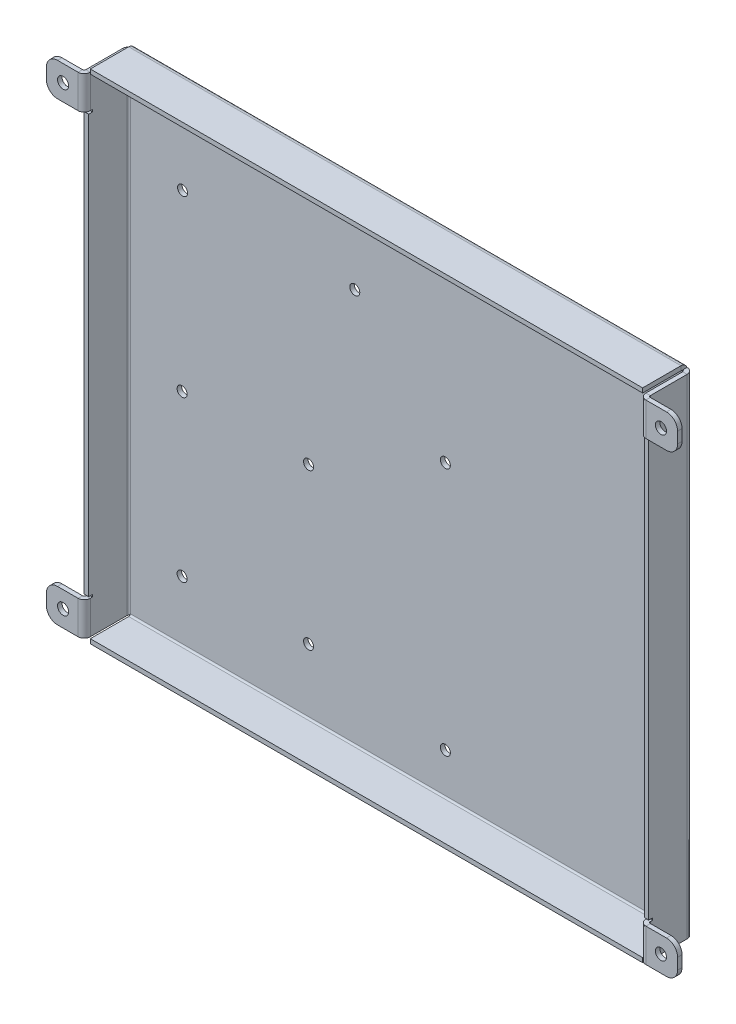
SolidWorks part; units mm, degrees
note: The reader was unsure of these and kept them because the rebuilt part matched: flange length of "Edge-Flange1", "Edge-Flange2", "Edge-Flange3", "Edge-Flange4", "Edge-Flange5", "Edge-Flange7", "Edge-Flange8".
ref_plane "Front Plane" through (0, 0, 0) normal (0, 0, 1) x (1, 0, 0)
ref_plane "Top Plane" through (0, 0, 0) normal (0, 1, 0) x (1, 0, 0)
ref_plane "Right Plane" through (0, 0, 0) normal (1, 0, 0) x (0, 0, -1)
sketch "Sketch1" plane through (0, 0, 0) normal (0, 0, 1) x (1, 0, 0)
  line L1 (-125, 110) -> (125, 110)
  line L2 (-125, 110) -> (-125, -110)
  line L3 (-125, -110) -> (125, -110)
  line L4 (125, 110) -> (125, -110)
  line L5 (0, -110) -> (0, 110) construction
  line L6 (-125, 0) -> (125, 0) construction
  point P0 (0, 0)
  dimension "D1" = 250
  dimension "D2" = 220
base flange "Base-Flange1" sketch "Sketch1" thickness 2 reverse thickness direction no parameters "D1"=0.7366
edge flange "Edge-Flange1" sketch "Sketch10" flange profiles "Sketch10", "Sketch11" flange angle 90 flange length 20 flange position material outside bend radius 0.7366 thickness 2 relief rectangular parameters "D6"=10, "D8"=1
sketch "Sketch10" plane through (125, 0, 0) normal (-1, 0, 0) x (0, -1, 0)
  line L2 (-110, 0) -> (-110, 18)
  line L3 (-110, 18) -> (110, 18)
  line L4 (110, 18) -> (110, 0)
  line L5 (110, 0) -> (-110, 0) construction
  line L6 (110, 0) -> (-110, 0)
sketch "Sketch11" plane through (-125, 0, 0) normal (1, 0, 0) x (0, 1, 0)
  line L0 (110, 0) -> (-110, 0) construction
  line L1 (110, 0) -> (-110, 0)
  line L2 (110, 0) -> (110, 18)
  line L3 (110, 18) -> (-110, 18)
  line L4 (-110, 18) -> (-110, 0)
bend "EdgeBend1" bend radius 0.7366 bend angle 90 parameters "D5"=1
bend "EdgeBend2" bend radius 0.7366 bend angle 90 parameters "D5"=2
edge flange "Edge-Flange2" sketch "Sketch14" flange angle 90 flange length 20 flange position material outside bend radius 0.7366 thickness 2 relief none parameters "D6"=10
sketch "Sketch14" plane through (0, 110, 0) normal (0, -1, 0) x (1, 0, 0)
  line L2 (-124.2634, 0) -> (-124.2634, 18)
  line L3 (-124.2634, 18) -> (124.2634, 18)
  line L4 (124.2634, 18) -> (124.2634, 0)
  line L5 (124.2634, 0) -> (-124.2634, 0) construction
  line L6 (124.2634, 0) -> (-124.2634, 0)
bend "EdgeBend3" bend radius 0.7366 bend angle 90 parameters "D5"=3
edge flange "Edge-Flange3" sketch "Sketch17" flange angle 90 flange length 20 flange position material outside bend radius 0.7366 thickness 2 relief none parameters "D6"=10
sketch "Sketch17" plane through (0, -110, 0) normal (0, -1, 0) x (1, 0, 0)
  line L0 (-124.2634, 0) -> (124.2634, 0) construction
  line L1 (-124.2634, 0) -> (124.2634, 0)
  line L2 (-124.2634, 0) -> (-124.2634, 18)
  line L3 (-124.2634, 18) -> (124.2634, 18)
  line L4 (124.2634, 18) -> (124.2634, 0)
bend "EdgeBend4" bend radius 0.7366 bend angle 90 parameters "D5"=4
edge flange "Edge-Flange4" sketch "Sketch20" flange angle 90 flange length 17 flange position material outside bend radius 0.7366 thickness 2 relief rectangular parameters "D6"=10
sketch "Sketch20" plane through (127, 0, 18) normal (0, 0, 1) x (0, -1, 0)
  line L0 (110, 0) -> (-110, 0) construction
  line L1 (110, 0) -> (95, 0)
  line L2 (95, 0) -> (95, 10)
  line L3 (100, 15) -> (105, 15)
  line L4 (110, 10) -> (110, 0)
  line L5 (110, 15) -> (95, 0) construction
  circle A0 centre (102.5, 7.5) radius 2.5
  arc A1 (105, 15) -> (110, 10) centre (105, 10) cw
  arc A2 (95, 10) -> (100, 15) centre (100, 10) cw
  point P12 (95, 15)
  dimension "D2" = 5
  dimension "D3" = 5
  dimension "D1" = 15
bend "EdgeBend5" bend radius 0.7366 bend angle 90 parameters "D5"=5
edge flange "Edge-Flange5" sketch "Sketch23" flange angle 90 flange length 17 flange position material outside bend radius 0.7366 thickness 2 relief rectangular parameters "D6"=10
sketch "Sketch23" plane through (127, 0, 18) normal (0, 0, 1) x (0, -1, 0)
  line L2 (-110, 0) -> (-110, 10)
  line L3 (-105, 15) -> (-100, 15)
  line L4 (-95, 10) -> (-95, 0)
  line L7 (94, 0) -> (-110, 0) construction
  line L8 (-95, 0) -> (-110, 0)
  line L9 (-110, 15) -> (-95, 0) construction
  circle A0 centre (-102.5, 7.5) radius 2.5
  arc A1 (-100, 15) -> (-95, 10) centre (-100, 10) cw
  arc A2 (-110, 10) -> (-105, 15) centre (-105, 10) cw
  point P9 (-95, 15)
  dimension "D2" = 5
  dimension "D3" = 5
  dimension "D1" = 15
bend "EdgeBend6" bend radius 0.7366 bend angle 90 parameters "D5"=6
edge flange "Edge-Flange7" sketch "Sketch30" flange angle 90 flange length 17 flange position material outside bend radius 0.7366 thickness 2 relief rectangular parameters "D6"=10
sketch "Sketch30" plane through (-127, 0, 18) normal (0, 0, 1) x (0, 1, 0)
  line L0 (110, 0) -> (-110, 0) construction
  line L1 (-95, 0) -> (-110, 0)
  line L2 (-110, 0) -> (-110, 10)
  line L3 (-105, 15) -> (-100, 15)
  line L4 (-95, 10) -> (-95, 0)
  line L5 (-110, 0) -> (-95, 15) construction
  circle A0 centre (-102.5, 7.5) radius 2.5
  arc A1 (-100, 15) -> (-95, 10) centre (-100, 10) cw
  arc A2 (-110, 10) -> (-105, 15) centre (-105, 10) cw
  point P12 (-110, 15)
  dimension "D2" = 5
  dimension "D3" = 5
  dimension "D1" = 15
bend "EdgeBend8" bend radius 0.7366 bend angle 90 parameters "D5"=7
edge flange "Edge-Flange8" sketch "Sketch33" flange angle 90 flange length 17 flange position material outside bend radius 0.7366 thickness 2 relief rectangular parameters "D6"=10
sketch "Sketch33" plane through (-127, 0, 18) normal (0, 0, 1) x (0, 1, 0)
  line L2 (95, 0) -> (95, 10)
  line L3 (100, 15) -> (105, 15)
  line L4 (110, 10) -> (110, 0)
  line L7 (110, 0) -> (-94, 0) construction
  line L8 (110, 0) -> (95, 0)
  line L9 (110, 15) -> (95, 0) construction
  circle A0 centre (102.5, 7.5) radius 2.5
  arc A1 (105, 15) -> (110, 10) centre (105, 10) cw
  arc A2 (95, 10) -> (100, 15) centre (100, 10) cw
  point P12 (95, 15)
  dimension "D2" = 5
  dimension "D3" = 5
  dimension "D1" = 15
bend "EdgeBend9" bend radius 0.7366 bend angle 90 parameters "D5"=8
sketch "Sketch34" plane through (0, 0, 0) normal (0, 0, 1) x (1, 0, 0)
  circle A0 centre (-44.05, -11) radius 2.25
  circle A1 centre (-44.05, -80.9579) radius 2.25
  circle A2 centre (-100.95, -83) radius 2.25
  circle A3 centre (-100.95, -11) radius 2.25
  dimension "D1" = 4.5
  dimension "D2" = 4.5
  dimension "D3" = 4.5
  dimension "D4" = 4.5
extrude "Cut-Extrude1" cut sketch "Sketch34" against normal blind 10
sketch "Sketch35" plane through (0, 0, -2) normal (0, 0, -1) x (-1, 0, 0)
  circle A0 centre (100.75, 67.5) radius 2.25
  circle A1 centre (23.25, 67.5) radius 2.25
  circle A2 centre (-110, 90.5) radius 2.25
  circle A3 centre (-17.5, 20.5) radius 2.25
  circle A4 centre (-110, -21.5) radius 2.25
  circle A5 centre (-17.5, -91.5) radius 2.25
  dimension "D1" = 4.5
  dimension "D2" = 4.5
  dimension "D3" = 4.5
  dimension "D4" = 4.5
  dimension "D5" = 4.5
  dimension "D6" = 4.5
extrude "Cut-Extrude2" cut sketch "Sketch35" against normal blind 10
sketch "Bend-Lines1" [suppressed] plane through (0, 0, 0) normal (0, 1, 0) x (1, 0, 0)
sketch "Bounding-Box1" [suppressed] plane through (0, 0, 0) normal (0, 1, 0) x (1, 0, 0)
sheet metal parameters "Sheet-Metal1" thickness 2 parameters "D1"=0.7366
flat pattern "Flat-Pattern1" [suppressed]
sketch "Bend-Lines2" plane through (0, 0, 0) normal (0, 1, 0) x (1, 0, 0)
sketch3d "Bounding-Box2" [suppressed]
  line L0 (150, -87.5, 0) -> (-150, -87.5, 0) construction
  line L1 (150, 87.5, 0) -> (-150, 87.5, 0) construction
  line L2 (150, -87.5, 0) -> (150, 87.5, 0) construction
  line L3 (-150, -87.5, 0) -> (-150, 87.5, 0) construction
sheet metal parameters "Sheet-Metal2" thickness 2 parameters "D1"=0.7366
flat pattern "Flat-Pattern1"
sketch "Bend-Lines2" plane through (0, 0, 0) normal (0, 0, 1) x (1, 0, 0)
  line L0 (-150.3132, 87.5) -> (-150.3132, -87.5) construction
  line L1 (150.3132, -87.5) -> (150.3132, 87.5) construction
  line L2 (-150.3132, 87.5) -> (-150.3132, -87.5) construction
  line L3 (150.3132, -87.5) -> (150.3132, 87.5) construction
sketch3d "Bounding-Box2" [suppressed]
  line L0 (-168.6263, -87.5, 0) -> (168.6263, -87.5, 0) construction
  line L1 (-168.6263, 87.5, 0) -> (168.6263, 87.5, 0) construction
  line L2 (-168.6263, -87.5, 0) -> (-168.6263, 87.5, 0) construction
  line L3 (168.6263, -87.5, 0) -> (168.6263, 87.5, 0) construction
bend of the flat pattern "Flatten-<EdgeBend1>1"
bend of the flat pattern "Flatten-<EdgeBend2>1"
sheet metal parameters "Sheet-Metal3" thickness 2 parameters "D1"=0.7366
flat pattern "Flat-Pattern1"
sketch "Bend-Lines2" plane through (0, 0, 0) normal (0, 0, 1) x (1, 0, 0)
  line L0 (-150.3132, 87.5) -> (-150.3132, -87.5) construction
  line L1 (150.3132, -87.5) -> (150.3132, 87.5) construction
  line L2 (-150.3132, 87.5) -> (-150.3132, -87.5) construction
  line L3 (150.3132, -87.5) -> (150.3132, 87.5) construction
  line L4 (149.2634, 87.8132) -> (-149.2634, 87.8132) construction
  line L5 (149.2634, 87.8132) -> (-149.2634, 87.8132) construction
sketch3d "Bounding-Box2" [suppressed]
  line L0 (-168.6263, -87.5, 0) -> (168.6263, -87.5, 0) construction
  line L1 (-168.6263, 106.1263, 0) -> (168.6263, 106.1263, 0) construction
  line L2 (-168.6263, -87.5, 0) -> (-168.6263, 106.1263, 0) construction
  line L3 (168.6263, -87.5, 0) -> (168.6263, 106.1263, 0) construction
bend of the flat pattern "Flatten-<EdgeBend1>1"
bend of the flat pattern "Flatten-<EdgeBend2>1"
bend of the flat pattern "Flatten-<EdgeBend3>1"
sheet metal parameters "Sheet-Metal4" thickness 2 parameters "D1"=0.7366
flat pattern "Flat-Pattern1"
sketch "Bend-Lines2" plane through (0, 0, 0) normal (0, 0, 1) x (1, 0, 0)
  line L0 (-150.3132, 110) -> (-150.3132, -110) construction
  line L1 (150.3132, -110) -> (150.3132, 110) construction
  line L2 (-150.3132, 110) -> (-150.3132, -110) construction
  line L3 (150.3132, -110) -> (150.3132, 110) construction
  line L4 (149.2634, 110.3132) -> (-149.2634, 110.3132) construction
  line L5 (149.2634, 110.3132) -> (-149.2634, 110.3132) construction
  line L6 (-149.2634, -110.3132) -> (149.2634, -110.3132) construction
  line L7 (-149.2634, -110.3132) -> (149.2634, -110.3132) construction
sketch3d "Bounding-Box2" [suppressed]
  line L0 (-168.6263, -128.6263, 0) -> (168.6263, -128.6263, 0) construction
  line L1 (-168.6263, 128.6263, 0) -> (168.6263, 128.6263, 0) construction
  line L2 (-168.6263, -128.6263, 0) -> (-168.6263, 128.6263, 0) construction
  line L3 (168.6263, -128.6263, 0) -> (168.6263, 128.6263, 0) construction
bend of the flat pattern "Flatten-<EdgeBend1>1"
bend of the flat pattern "Flatten-<EdgeBend2>1"
bend of the flat pattern "Flatten-<EdgeBend3>1"
bend of the flat pattern "Flatten-<EdgeBend4>1"
sheet metal parameters "Sheet-Metal5" thickness 2 parameters "D1"=0.7366
flat pattern "Flat-Pattern1"
sketch "Bend-Lines2" plane through (0, 0, 0) normal (0, 0, 1) x (1, 0, 0)
  line L0 (-150.3132, 110) -> (-150.3132, -110) construction
  line L1 (150.3132, -110) -> (150.3132, 110) construction
  line L2 (-150.3132, 110) -> (-150.3132, -110) construction
  line L3 (150.3132, -110) -> (150.3132, 110) construction
  line L4 (149.2634, 110.3132) -> (-149.2634, 110.3132) construction
  line L5 (149.2634, 110.3132) -> (-149.2634, 110.3132) construction
  line L6 (-149.2634, -110.3132) -> (149.2634, -110.3132) construction
  line L7 (-149.2634, -110.3132) -> (149.2634, -110.3132) construction
  line L8 (168.9395, -110) -> (168.9395, -93.0621) construction
  line L9 (168.9395, -110) -> (168.9395, -93.0621) construction
sketch3d "Bounding-Box2" [suppressed]
  line L0 (-168.6263, -128.6263, 0) -> (184.2527, -128.6263, 0) construction
  line L1 (-168.6263, 128.6263, 0) -> (184.2527, 128.6263, 0) construction
  line L2 (-168.6263, -128.6263, 0) -> (-168.6263, 128.6263, 0) construction
  line L3 (184.2527, -128.6263, 0) -> (184.2527, 128.6263, 0) construction
bend of the flat pattern "Flatten-<EdgeBend1>1"
bend of the flat pattern "Flatten-<EdgeBend2>1"
bend of the flat pattern "Flatten-<EdgeBend3>1"
bend of the flat pattern "Flatten-<EdgeBend4>1"
bend of the flat pattern "Flatten-<EdgeBend5>1"
sheet metal parameters "Sheet-Metal6" thickness 2 parameters "D1"=0.7366
flat pattern "Flat-Pattern1"
sketch "Bend-Lines2" plane through (0, 0, 0) normal (0, 0, 1) x (1, 0, 0)
  line L0 (-150.3132, 110) -> (-150.3132, -110) construction
  line L1 (150.3132, -110) -> (150.3132, 110) construction
  line L2 (-150.3132, 110) -> (-150.3132, -110) construction
  line L3 (150.3132, -110) -> (150.3132, 110) construction
  line L4 (149.2634, 110.3132) -> (-149.2634, 110.3132) construction
  line L5 (149.2634, 110.3132) -> (-149.2634, 110.3132) construction
  line L6 (-149.2634, -110.3132) -> (149.2634, -110.3132) construction
  line L7 (-149.2634, -110.3132) -> (149.2634, -110.3132) construction
  line L8 (168.9395, -110) -> (168.9395, -95) construction
  line L9 (168.9395, -110) -> (168.9395, -95) construction
  line L10 (168.9395, 95) -> (168.9395, 110) construction
  line L11 (168.9395, 95) -> (168.9395, 110) construction
sketch3d "Bounding-Box2" [suppressed]
  line L0 (-168.6263, 128.6264, 0) -> (184.2527, 128.6263, 0) construction
  line L1 (-168.6263, -128.6263, 0) -> (184.2526, -128.6263, 0) construction
  line L2 (-168.6263, 128.6264, 0) -> (-168.6263, -128.6263, 0) construction
  line L3 (184.2527, 128.6263, 0) -> (184.2526, -128.6263, 0) construction
bend of the flat pattern "Flatten-<EdgeBend1>1"
bend of the flat pattern "Flatten-<EdgeBend2>1"
bend of the flat pattern "Flatten-<EdgeBend3>1"
bend of the flat pattern "Flatten-<EdgeBend4>1"
bend of the flat pattern "Flatten-<EdgeBend5>1"
bend of the flat pattern "Flatten-<EdgeBend6>1"
sheet metal parameters "Sheet-Metal8" thickness 2 parameters "D1"=0.7366
flat pattern "Flat-Pattern1"
sketch "Bend-Lines2" plane through (0, 0, 0) normal (0, 0, 1) x (1, 0, 0)
  line L0 (-150.3132, 110) -> (-150.3132, -110) construction
  line L1 (150.3132, -110) -> (150.3132, 110) construction
  line L2 (-150.3132, 110) -> (-150.3132, -110) construction
  line L3 (150.3132, -110) -> (150.3132, 110) construction
  line L4 (149.2634, 110.3132) -> (-149.2634, 110.3132) construction
  line L5 (149.2634, 110.3132) -> (-149.2634, 110.3132) construction
  line L6 (-149.2634, -110.3132) -> (149.2634, -110.3132) construction
  line L7 (-149.2634, -110.3132) -> (149.2634, -110.3132) construction
  line L8 (168.9395, -110) -> (168.9395, -95) construction
  line L9 (168.9395, -110) -> (168.9395, -95) construction
  line L10 (168.9395, 95) -> (168.9395, 110) construction
  line L11 (168.9395, 95) -> (168.9395, 110) construction
  line L12 (-168.9395, -95) -> (-168.9395, -110) construction
  line L13 (-168.9395, -95) -> (-168.9395, -110) construction
sketch3d "Bounding-Box2" [suppressed]
  line L0 (-184.2526, 128.6264, 0) -> (184.2527, 128.6263, 0) construction
  line L1 (-184.2527, -128.6263, 0) -> (184.2526, -128.6263, 0) construction
  line L2 (-184.2526, 128.6264, 0) -> (-184.2527, -128.6263, 0) construction
  line L3 (184.2527, 128.6263, 0) -> (184.2526, -128.6263, 0) construction
bend of the flat pattern "Flatten-<EdgeBend1>1"
bend of the flat pattern "Flatten-<EdgeBend2>1"
bend of the flat pattern "Flatten-<EdgeBend3>1"
bend of the flat pattern "Flatten-<EdgeBend4>1"
bend of the flat pattern "Flatten-<EdgeBend5>1"
bend of the flat pattern "Flatten-<EdgeBend6>1"
bend of the flat pattern "Flatten-<EdgeBend8>1"
sheet metal parameters "Sheet-Metal9" thickness 2 parameters "D1"=0.7366
flat pattern "Flat-Pattern1"
sketch "Bend-Lines2" plane through (0, 0, 0) normal (0, 0, 1) x (1, 0, 0)
  line L0 (-150.3132, 110) -> (-150.3132, -110) construction
  line L1 (150.3132, -110) -> (150.3132, 110) construction
  line L2 (-150.3132, 110) -> (-150.3132, -110) construction
  line L3 (150.3132, -110) -> (150.3132, 110) construction
  line L4 (149.2634, 110.3132) -> (-149.2634, 110.3132) construction
  line L5 (149.2634, 110.3132) -> (-149.2634, 110.3132) construction
  line L6 (-149.2634, -110.3132) -> (149.2634, -110.3132) construction
  line L7 (-149.2634, -110.3132) -> (149.2634, -110.3132) construction
  line L8 (168.9395, -110) -> (168.9395, -95) construction
  line L9 (168.9395, -110) -> (168.9395, -95) construction
  line L10 (168.9395, 95) -> (168.9395, 110) construction
  line L11 (168.9395, 95) -> (168.9395, 110) construction
  line L12 (-168.9395, -95) -> (-168.9395, -110) construction
  line L13 (-168.9395, -95) -> (-168.9395, -110) construction
  line L14 (-168.9395, 110) -> (-168.9395, 95) construction
  line L15 (-168.9395, 110) -> (-168.9395, 95) construction
sketch3d "Bounding-Box2" [suppressed]
  line L0 (-184.2526, 128.6264, 0) -> (184.2527, 128.6263, 0) construction
  line L1 (-184.2527, -128.6263, 0) -> (184.2526, -128.6263, 0) construction
  line L2 (-184.2526, 128.6264, 0) -> (-184.2527, -128.6263, 0) construction
  line L3 (184.2527, 128.6263, 0) -> (184.2526, -128.6263, 0) construction
bend of the flat pattern "Flatten-<EdgeBend1>1"
bend of the flat pattern "Flatten-<EdgeBend2>1"
bend of the flat pattern "Flatten-<EdgeBend3>1"
bend of the flat pattern "Flatten-<EdgeBend4>1"
bend of the flat pattern "Flatten-<EdgeBend5>1"
bend of the flat pattern "Flatten-<EdgeBend6>1"
bend of the flat pattern "Flatten-<EdgeBend8>1"
bend of the flat pattern "Flatten-<EdgeBend9>1"
sheet metal parameters "Sheet-Metal10" thickness 2 parameters "D1"=0.7366
flat pattern "Flat-Pattern1"
sketch "Bend-Lines2" plane through (0, 0, 0) normal (0, 0, 1) x (1, 0, 0)
  line L0 (-125.3132, 110) -> (-125.3132, -110) construction
  line L1 (125.3132, -110) -> (125.3132, 110) construction
  line L2 (-125.3132, 110) -> (-125.3132, -110) construction
  line L3 (125.3132, -110) -> (125.3132, 110) construction
  line L4 (124.2634, 110.3132) -> (-124.2634, 110.3132) construction
  line L5 (124.2634, 110.3132) -> (-124.2634, 110.3132) construction
  line L6 (-124.2634, -110.3132) -> (124.2634, -110.3132) construction
  line L7 (-124.2634, -110.3132) -> (124.2634, -110.3132) construction
  line L8 (143.9395, -110) -> (143.9395, -95) construction
  line L9 (143.9395, -110) -> (143.9395, -95) construction
  line L10 (143.9395, 95) -> (143.9395, 110) construction
  line L11 (143.9395, 95) -> (143.9395, 110) construction
  line L12 (-143.9395, -95) -> (-143.9395, -110) construction
  line L13 (-143.9395, -95) -> (-143.9395, -110) construction
  line L14 (-143.9395, 110) -> (-143.9395, 95) construction
  line L15 (-143.9395, 110) -> (-143.9395, 95) construction
sketch3d "Bounding-Box2" [suppressed]
  line L0 (-159.2526, 128.6263, 0) -> (159.2527, 128.6263, 0) construction
  line L1 (-159.2527, -128.6263, 0) -> (159.2526, -128.6263, 0) construction
  line L2 (-159.2526, 128.6263, 0) -> (-159.2527, -128.6263, 0) construction
  line L3 (159.2527, 128.6263, 0) -> (159.2526, -128.6263, 0) construction
bend of the flat pattern "Flatten-<EdgeBend1>1"
bend of the flat pattern "Flatten-<EdgeBend2>1"
bend of the flat pattern "Flatten-<EdgeBend3>1"
bend of the flat pattern "Flatten-<EdgeBend4>1"
bend of the flat pattern "Flatten-<EdgeBend5>1"
bend of the flat pattern "Flatten-<EdgeBend6>1"
bend of the flat pattern "Flatten-<EdgeBend8>1"
bend of the flat pattern "Flatten-<EdgeBend9>1"
sheet metal parameters "Sheet-Metal11" thickness 2 parameters "D1"=0.7366
flat pattern "Flat-Pattern1"
sketch "Bend-Lines2" plane through (0, 0, 0) normal (0, 0, 1) x (1, 0, 0)
  line L0 (-125.3132, 110) -> (-125.3132, -110) construction
  line L1 (125.3132, -110) -> (125.3132, 110) construction
  line L2 (-125.3132, 110) -> (-125.3132, -110) construction
  line L3 (125.3132, -110) -> (125.3132, 110) construction
  line L4 (124.2634, 110.3132) -> (-124.2634, 110.3132) construction
  line L5 (124.2634, 110.3132) -> (-124.2634, 110.3132) construction
  line L6 (-124.2634, -110.3132) -> (124.2634, -110.3132) construction
  line L7 (-124.2634, -110.3132) -> (124.2634, -110.3132) construction
  line L8 (143.9395, -110) -> (143.9395, -95) construction
  line L9 (143.9395, -110) -> (143.9395, -95) construction
  line L10 (143.9395, 95) -> (143.9395, 110) construction
  line L11 (143.9395, 95) -> (143.9395, 110) construction
  line L12 (-143.9395, -95) -> (-143.9395, -110) construction
  line L13 (-143.9395, -95) -> (-143.9395, -110) construction
  line L14 (-143.9395, 110) -> (-143.9395, 95) construction
  line L15 (-143.9395, 110) -> (-143.9395, 95) construction
sketch3d "Bounding-Box2" [suppressed]
  line L0 (-159.2526, 128.6263, 0) -> (159.2527, 128.6263, 0) construction
  line L1 (-159.2527, -128.6263, 0) -> (159.2526, -128.6263, 0) construction
  line L2 (-159.2526, 128.6263, 0) -> (-159.2527, -128.6263, 0) construction
  line L3 (159.2527, 128.6263, 0) -> (159.2526, -128.6263, 0) construction
bend of the flat pattern "Flatten-<EdgeBend1>1"
bend of the flat pattern "Flatten-<EdgeBend2>1"
bend of the flat pattern "Flatten-<EdgeBend3>1"
bend of the flat pattern "Flatten-<EdgeBend4>1"
bend of the flat pattern "Flatten-<EdgeBend5>1"
bend of the flat pattern "Flatten-<EdgeBend6>1"
bend of the flat pattern "Flatten-<EdgeBend8>1"
bend of the flat pattern "Flatten-<EdgeBend9>1"
